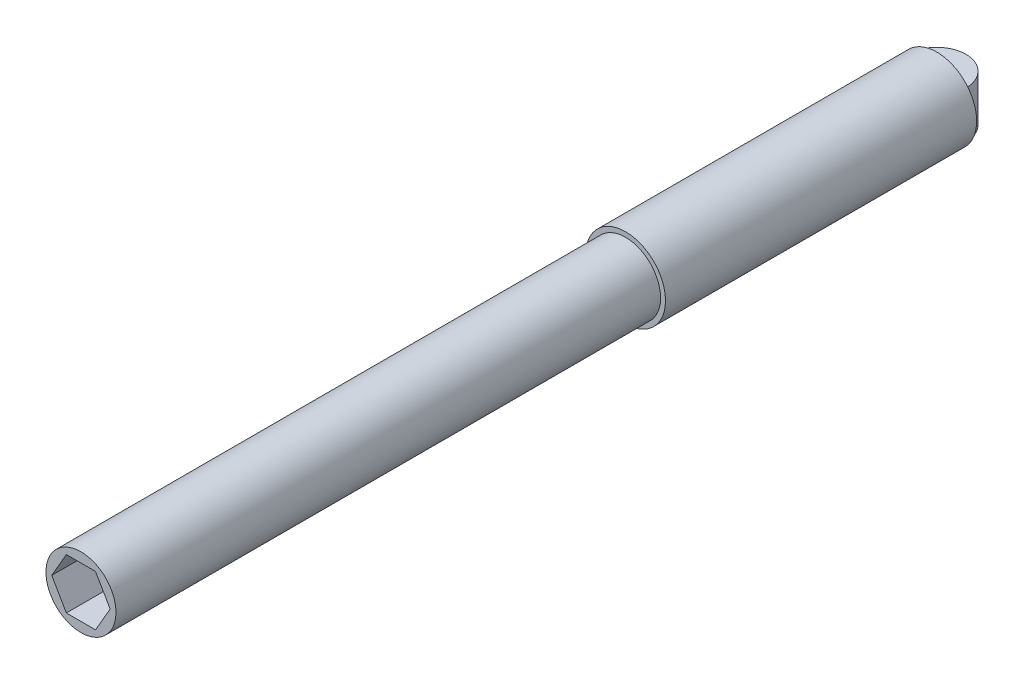
SolidWorks part; units mm, degrees
ref_plane "Front Plane" through (0, 0, 0) normal (0, 0, 1) x (1, 0, 0)
ref_plane "Top Plane" through (0, 0, 0) normal (0, 1, 0) x (1, 0, 0)
ref_plane "Right Plane" through (0, 0, 0) normal (1, 0, 0) x (0, 0, -1)
sketch "Sketch1" plane through (0, 0, 0) normal (0, 0, 1) x (1, 0, 0)
  circle A0 centre (0, 0) radius 1.025
  dimension "D1" = 2.05
extrude "Boss-Extrude1" add sketch "Sketch1" along normal blind 12
sketch "Sketch2" plane through (0, 0, 12) normal (0, 0, 1) x (1, 0, 0)
  line L0 (0, 0) -> (1.025, 0)
  line L2 (0.866, 0) -> (0.433, 0.75)
  line L3 (0.433, 0.75) -> (-0.433, 0.75)
  line L4 (-0.433, 0.75) -> (-0.866, 0)
  line L5 (-0.866, 0) -> (-0.433, -0.75)
  line L6 (-0.433, -0.75) -> (0.433, -0.75)
  line L7 (0.433, -0.75) -> (0.866, 0)
  circle A0 centre (0, 0) radius 1.025 construction
  circle A1 centre (0, 0) radius 0.75 construction
extrude "Cut-Extrude1" cut sketch "Sketch2" against normal blind 7 contours L6 L7 L2 L3 L4 L5 region at (0.6297, -0.3635, 12)
sketch "Sketch3" plane through (0, 0, 0) normal (0, 0, -1) x (-1, 0, 0)
  circle A0 centre (0, 0) radius 1.025
extrude "Boss-Extrude2" add sketch "Sketch3" along normal blind 4
sketch "Sketch4" plane through (0, 0, -4) normal (0, 0, -1) x (-1, 0, 0)
  line L0 (0, 0) -> (1.025, 0)
  circle A0 centre (0, 0) radius 1.025 construction
ref_plane "Plane3" through (0, 0, 0) normal (0, 1, 0) x (1, 0, 0)
sketch "Sketch5" plane through (0, 0, 0) normal (0, 1, 0) x (1, 0, 0)
  line L0 (1.025, 4) -> (-1.025, 4) construction
  line L1 (-1, 4) -> (1, 4)
  circle A0 centre (0, 4) radius 1
  dimension "D1" = 2
sketch "Sketch6" plane through (0, 0, 12) normal (0, 0, 1) x (1, 0, 0)
  line L1 (0.866, 0) -> (0.433, 0.75)
  line L2 (0.433, 0.75) -> (-0.433, 0.75)
  line L3 (-0.433, 0.75) -> (-0.866, 0)
  line L4 (-0.866, 0) -> (-0.433, -0.75)
  line L5 (-0.433, -0.75) -> (0.433, -0.75)
  line L6 (0.433, -0.75) -> (0.866, 0)
  circle A0 centre (0, 0) radius 0.75 construction
  circle A1 centre (0, 0) radius 1.025
extrude "Boss-Extrude5" add sketch "Sketch6" along normal blind 7
sketch "Sketch7" plane through (0, 0, -4) normal (0, 0, -1) x (-1, 0, 0)
  circle A0 centre (0, 0) radius 1.025
extrude "Boss-Extrude6" add sketch "Sketch7" along normal blind 2
sketch "Sketch8" plane through (0, 0, 0) normal (0, 1, 0) x (1, 0, 0)
  line L0 (1.025, 6) -> (-1.025, 6) construction
  line L1 (-0.75, 6) -> (0.75, 6)
  circle A0 centre (0, 6) radius 0.75
  dimension "D1" = 1.5
extrude "Boss-Extrude8" add sketch "Sketch8" along normal blind 0.6 and the other way blind 0.6 contours L1 A0 region at (0, 0, -6.3183)
sketch "Sketch9" plane through (0, 0, 19) normal (0, 0, 1) x (1, 0, 0)
  circle A0 centre (0, 0) radius 1.025
extrude "Cut-Extrude3" cut sketch "Sketch9" against normal blind 17
sketch "Sketch10" plane through (0, 0, 2) normal (0, 0, 1) x (1, 0, 0)
  line L7 (0.7506, 0) -> (0.3753, 0.65)
  line L8 (0.3753, 0.65) -> (-0.3753, 0.65)
  line L9 (-0.3753, 0.65) -> (-0.7506, 0)
  line L10 (-0.7506, 0) -> (-0.3753, -0.65)
  line L11 (-0.3753, -0.65) -> (0.3753, -0.65)
  line L12 (0.3753, -0.65) -> (0.7506, 0)
  circle A0 centre (0, 0) radius 0.65 construction
  circle A1 centre (0, 0) radius 0.9
  dimension "D1" = 1.8
extrude "Boss-Extrude12" add sketch "Sketch10" along normal blind 14 contours L11 L12 L7 L8 L9 L10 | A1 region at (0, 0, 2)
sketch "Sketch12" plane through (0, 0, 16) normal (0, 0, 1) x (1, 0, 0)
  line L1 (0.7506, 0) -> (0.3753, 0.65)
  line L2 (0.3753, 0.65) -> (-0.3753, 0.65)
  line L3 (-0.3753, 0.65) -> (-0.7506, 0)
  line L4 (-0.7506, 0) -> (-0.3753, -0.65)
  line L5 (-0.3753, -0.65) -> (0.3753, -0.65)
  line L6 (0.3753, -0.65) -> (0.7506, 0)
  circle A0 centre (0, 0) radius 0.65 construction
